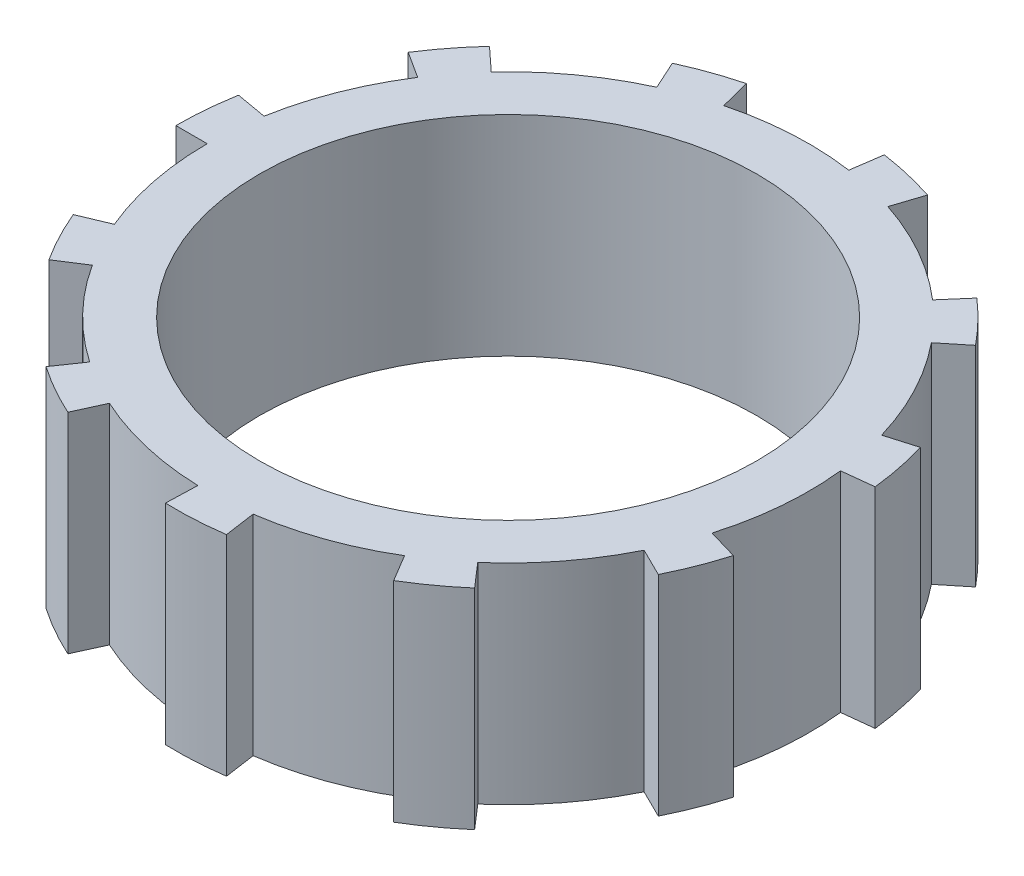
SolidWorks part; units mm, degrees
ref_plane "Front Plane" through (0, 0, 0) normal (0, 0, 1) x (1, 0, 0)
ref_plane "Top Plane" through (0, 0, 0) normal (0, 1, 0) x (1, 0, 0)
ref_plane "Right Plane" through (0, 0, 0) normal (1, 0, 0) x (0, 0, -1)
sketch "Sketch1" plane through (0, 0, 0) normal (0, 1, 0) x (1, 0, 0)
  circle A0 centre (0, 0) radius 23.755
  circle A1 centre (0, 0) radius 28.755
  dimension "D1" = 47.51
  dimension "D2" = 5
extrude "Boss-Extrude1" add sketch "Sketch1" along normal blind 20
sketch "Sketch2" plane through (0, 0, 0) normal (0, 0, 1) x (1, 0, 0)
  line L0 (-28.755, 20) -> (-31.755, 20)
  line L1 (28.755, 20) -> (-28.755, 20) construction
  line L2 (-31.755, 20) -> (-31.755, 0)
  line L3 (-31.755, 0) -> (-28.755, 0)
  line L4 (-28.755, 0) -> (-28.755, 20)
  line L5 (-28.755, 20) -> (-28.755, 0) construction
  dimension "D1" = 3
ref_axis "Axis1" through (0, 20, 0) along (0, -1, 0)
revolve "Revolve1" add sketch "Sketch2" angle 10 about axis through (0, 20, 0) along (0, -1, 0)
pattern_circular "CirPattern1" count 11 over 360 about axis through (0, 20, 0) along (0, -1, 0) of "Revolve1"
